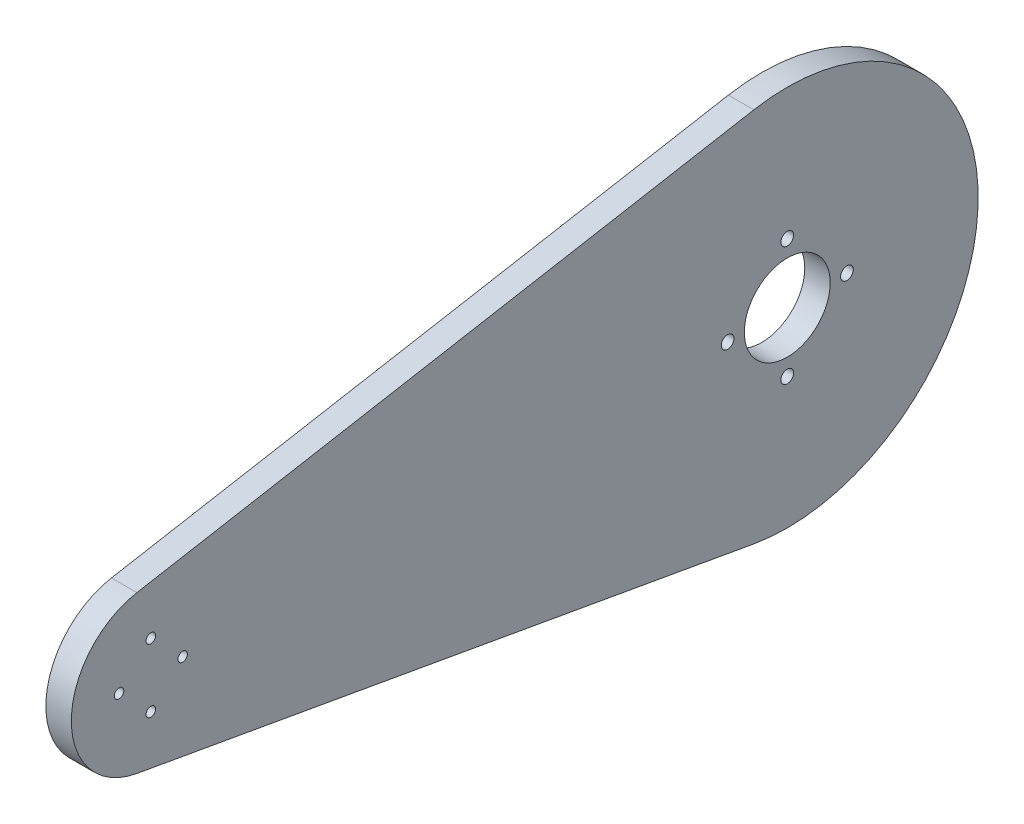
SolidWorks part; units mm, degrees
material "2024-T4"
ref_plane "Front Plane" through (0, 0, 0) normal (0, 0, 1) x (1, 0, 0)
ref_plane "Top Plane" through (0, 0, 0) normal (0, 1, 0) x (1, 0, 0)
ref_plane "Right Plane" through (0, 0, 0) normal (1, 0, 0) x (0, 0, -1)
sketch "Sketch1" plane through (0, 0, 0) normal (1, 0, 0) x (0, 0, -1)
  line L0 (0, 0) -> (-200, 0) construction
  line L1 (-204.375, 24.6142) -> (-10.5, 59.0741)
  line L2 (-204.375, -24.6142) -> (-10.5, -59.0741)
  circle A0 centre (0, 0) radius 13.5
  arc A1 (-10.5, -59.0741) -> (-10.5, 59.0741) centre (0, 0) ccw
  arc A2 (-204.375, 24.6142) -> (-204.375, -24.6142) centre (-200, 0) ccw
  dimension "D1" = 120
  dimension "D2" = 27
  dimension "D3" = 25
  dimension "D5" = 200
extrude "Boss-Extrude1" add sketch "Sketch1" along normal mid plane 8
sketch "Sketch2" plane through (4, 0, 0) normal (1, 0, 0) x (0, 0, -1)
  line L0 (0, 0) -> (0, 18.75) construction
  line L1 (-200, 0) -> (-210, 0) construction
  circle A0 centre (0, 18.75) radius 2
  circle A1 centre (18.75, 0) radius 2
  circle A2 centre (0, -18.75) radius 2
  circle A3 centre (-18.75, 0) radius 2
  circle A4 centre (-200, 0) radius 10 construction
  circle A5 centre (-210, 0) radius 1.5
  circle A6 centre (-200, 10) radius 1.5
  circle A7 centre (-190, 0) radius 1.5
  circle A8 centre (-200, -10) radius 1.5
  point P13 (0, 0)
  point P24 (-200, 0)
  dimension "D1" = 4
  dimension "D6" = 20
  dimension "D7" = 3
  dimension "D2" = 18.75
  dimension "D4" = 18.75
  dimension "D5" = 18.75
  dimension "D9" = 20
  dimension "D10" = 10
  dimension "D3" = 4
  dimension "D8" = 4
extrude "Cut-Extrude1" cut sketch "Sketch2" against normal through all
equation "\"D4@Sketch2\"=\"D2@Sketch2\""
equation "\"D5@Sketch2\"=\"D2@Sketch2\""
equation "\"shaft-diameter\"=20mm"
equation "\"key-length\"=12mm"
equation "\"key-width\"=4mm"
equation "\"flippershaft-wormgear-diameter\"= 35mm"
equation "\"shaft-ring-groove-depth\"=0.5mm"
equation "\"shaft-ring-groove-width\"= 1.3mm"
equation "\"mini-shaft-diameter\"= 12mm"
equation "\"mini-flipper-shaft-diameter\"= 26mm"
